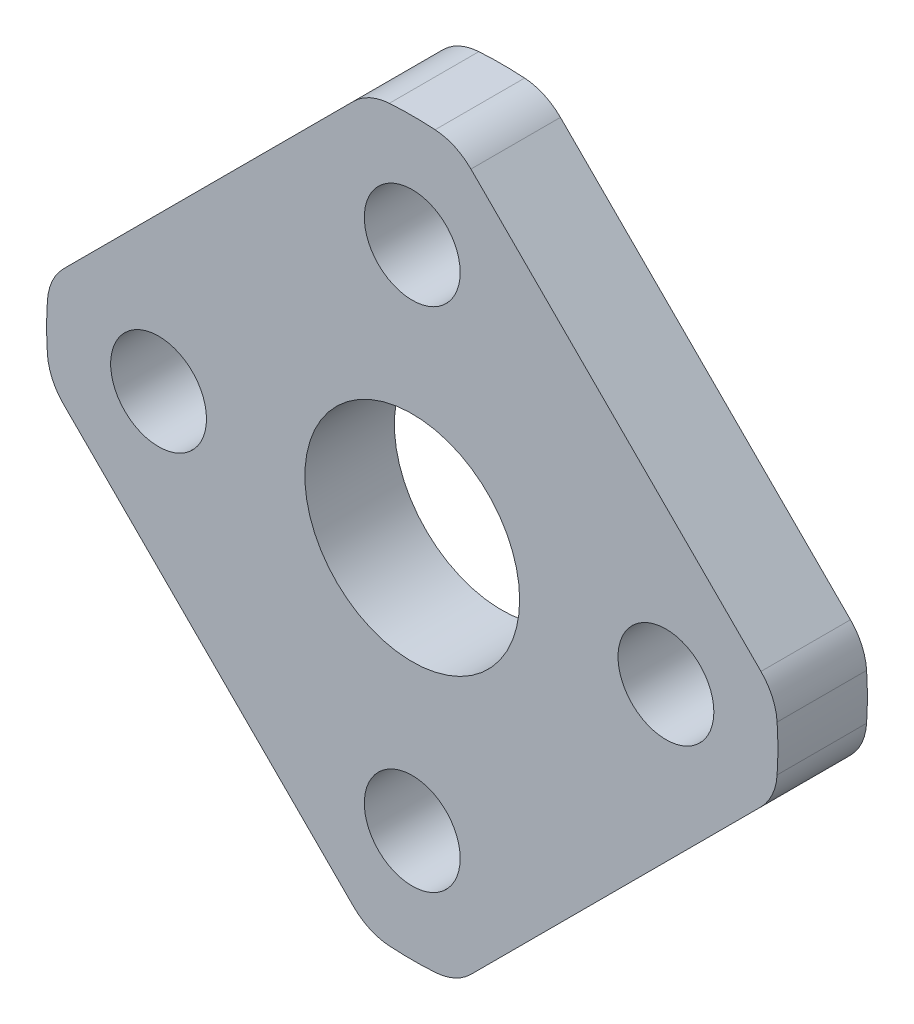
SolidWorks part; units mm, degrees
material "6061-T6 (SS)"
ref_plane "Front Plane" through (0, 0, 0) normal (0, 0, 1) x (1, 0, 0)
ref_plane "Top Plane" through (0, 0, 0) normal (0, 1, 0) x (1, 0, 0)
ref_plane "Right Plane" through (0, 0, 0) normal (1, 0, 0) x (0, 0, -1)
sketch "Sketch1" plane through (0, 0, 0) normal (0, 0, 1) x (1, 0, 0)
  line L5 (-2.0819, 12.3714) -> (-12.3714, 2.0819)
  line L6 (-12.3714, -2.0819) -> (-2.0819, -12.3714)
  line L10 (2.0819, -12.3714) -> (12.3714, -2.0819)
  line L11 (12.3714, 2.0819) -> (2.0819, 12.3714)
  circle A0 centre (0, -9) radius 1.7
  circle A1 centre (-9, 0) radius 1.7
  circle A2 centre (0, 9) radius 1.7
  circle A3 centre (9, 0) radius 1.7
  circle A16 centre (0, 0) radius 3.81
  arc A17 (-12.3714, 2.0819) -> (-12.9445, 0.8122) centre (-10.9784, 0.6889) ccw
  arc A18 (-12.9445, 0.8122) -> (-12.9445, -0.8122) centre (0, 0) ccw
  arc A19 (-12.9445, -0.8122) -> (-12.3714, -2.0819) centre (-10.9784, -0.6889) ccw
  arc A20 (-2.0819, -12.3714) -> (-0.8122, -12.9445) centre (-0.6889, -10.9784) ccw
  arc A21 (-0.8122, -12.9445) -> (0.8122, -12.9445) centre (0, 0) ccw
  arc A22 (0.8122, -12.9445) -> (2.0819, -12.3714) centre (0.6889, -10.9784) ccw
  arc A23 (12.3714, -2.0819) -> (12.9445, -0.8122) centre (10.9784, -0.6889) ccw
  arc A24 (12.9445, -0.8122) -> (12.9445, 0.8122) centre (0, 0) ccw
  arc A25 (12.9445, 0.8122) -> (12.3714, 2.0819) centre (10.9784, 0.6889) ccw
  arc A26 (2.0819, 12.3714) -> (0.8122, 12.9445) centre (0.6889, 10.9784) ccw
  arc A27 (0.8122, 12.9445) -> (-0.8122, 12.9445) centre (0, 0) ccw
  arc A28 (-0.8122, 12.9445) -> (-2.0819, 12.3714) centre (-0.6889, 10.9784) ccw
  point P0 (0, 0)
  point P6 (0, 0)
  point P67 (0, 0)
  dimension "D3" = 3.4
  dimension "D6" = 7.62
extrude "Boss-Extrude1" add sketch "Sketch1" along normal blind 3.175
